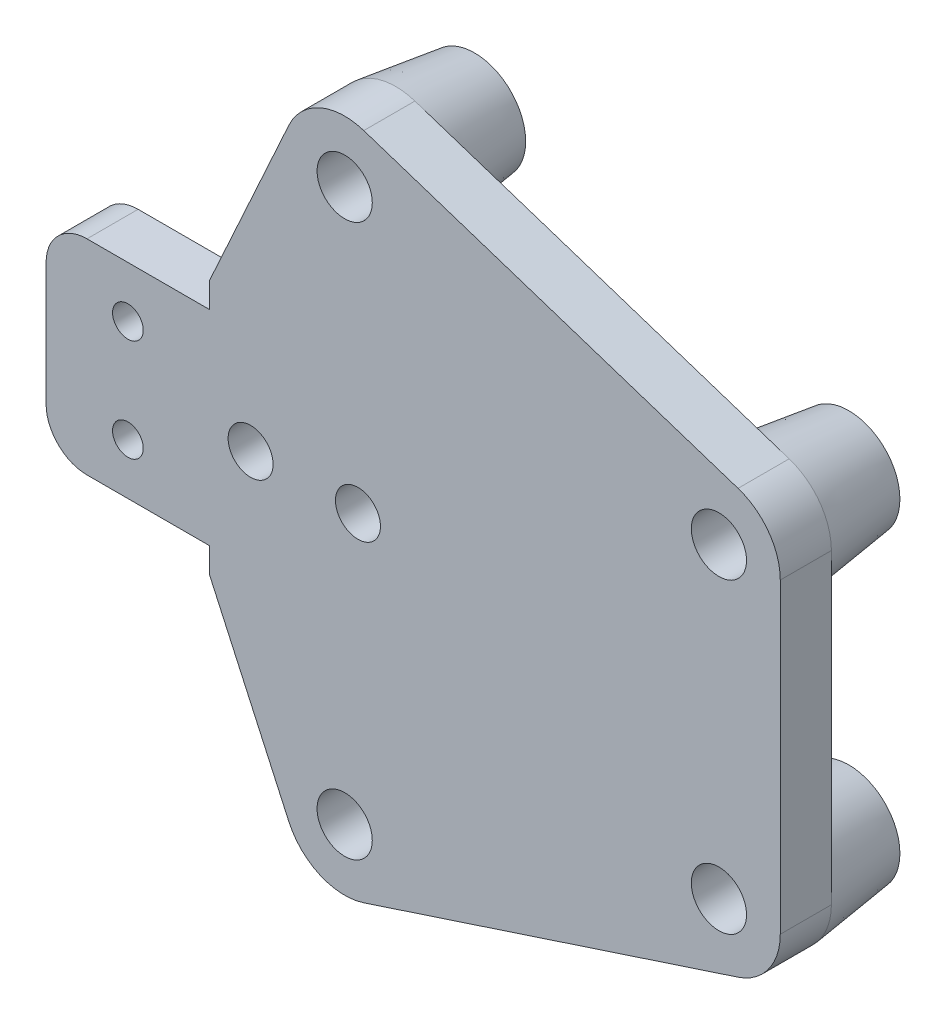
SolidWorks part; units mm, degrees
ref_plane "前视基准面" through (0, 0, 0) normal (0, 0, 1) x (1, 0, 0)
ref_plane "上视基准面" through (0, 0, 0) normal (0, 1, 0) x (1, 0, 0)
ref_plane "右视基准面" through (0, 0, 0) normal (1, 0, 0) x (0, 0, -1)
sketch "草图1" plane through (0, 0, 0) normal (0, 0, 1) x (1, 0, 0)
  line L0 (-612.4365, 0) -> (30009.3904, 0) construction
  line L1 (-611.4109, 10) -> (30010.416, 10) construction
  line L2 (-607.9921, -10) -> (30013.8348, -10) construction
  line L3 (0, -612.4365) -> (0, 30009.3904) construction
  line L4 (-10, -612.4365) -> (-10, 30009.3904) construction
  line L5 (10, -614.6741) -> (10, 30007.1528) construction
  line L6 (-24.3, 27) -> (-24.3, -27) construction
  line L7 (-16.4307, 32.7014) -> (20.1693, 20.7014)
  line L8 (24.3, 15) -> (24.3, -15)
  line L9 (-31.5, 12.5) -> (-31.5, -12.5)
  line L10 (-23.76, -29.4877) -> (-31.5, -12.5)
  line L11 (-31.5, 12.3) -> (-12, 12.3)
  line L12 (-31.5, 10.3) -> (-12, 10.3)
  line L13 (-12, 12.3) -> (-12, 10.3)
  line L14 (20.1693, -20.7014) -> (-16.4307, -32.7014)
  line L15 (-31.5, -10.3) -> (-12, -10.3)
  line L16 (-31.5, -12.3) -> (-12, -12.3)
  line L17 (-12, -12.3) -> (-12, -10.3)
  line L18 (-23.76, 29.4877) -> (-31.5, 12.5)
  line L19 (-33.5, 10) -> (-33.5, -10) construction
  line L20 (-47.5, 6) -> (-47.5, -6)
  line L21 (-43.5, 10) -> (-31.5, 10)
  line L22 (-43.5, -10) -> (-31.5, -10)
  circle A0 centre (18.3, 27) radius 11.5 construction
  circle A1 centre (-18.3, 27) radius 11.5 construction
  circle A2 centre (-18.3, -27) radius 11.5 construction
  circle A3 centre (18.3, 15) radius 11.5 construction
  circle A4 centre (18.3, 15) radius 2.7
  circle A5 centre (-18.3, 27) radius 6
  circle A6 centre (-16, 14) radius 1.7 construction
  circle A7 centre (18.3, 15) radius 5 construction
  circle A8 centre (-18.3, 27) radius 2.7
  circle A9 centre (-18.3, -27) radius 2.7
  circle A10 centre (-18.3, 27) radius 5 construction
  circle A11 centre (-18.3, -27) radius 5 construction
  circle A12 centre (18.3, 15) radius 6
  circle A13 centre (18.3, -15) radius 5 construction
  circle A14 centre (-16, -14) radius 1.7 construction
  circle A15 centre (-18.3, -27) radius 6
  circle A16 centre (-17, 0) radius 2.2
  circle A17 centre (-27.5, 0) radius 2.2
  circle A18 centre (-31, 18) radius 2.2 construction
  circle A19 centre (-31, -18) radius 2.2 construction
  circle A20 centre (18.3, -15) radius 11.5 construction
  circle A21 centre (18.3, -15) radius 6
  circle A22 centre (18.3, -15) radius 2.7
  circle A23 centre (-17, 0) radius 4 construction
  circle A24 centre (-39.5, 5) radius 1.5
  circle A25 centre (-39.5, -5) radius 1.5
  arc A26 (-47.5, -6) -> (-43.5, -10) centre (-43.5, -6) ccw
  arc A27 (-47.5, 6) -> (-43.5, 10) centre (-43.5, 6) cw
  point P48 (-31.5, 0)
  point P54 (-31.5, 0)
  point P82 (-47.5, -10)
  point P85 (-47.5, 10)
  dimension "D5" = 23
  dimension "D6" = 27
  dimension "D7" = 15
  dimension "D9" = 12
  dimension "D10" = 8
  dimension "D11" = 5.4
  dimension "D12" = 10
  dimension "D8" = 4.4
  dimension "D23" = 3.4
  dimension "D24" = 4.4
  dimension "D30" = 3
  dimension "D35" = 4
  dimension "D1" = 20
  dimension "D2" = 10
  dimension "D3" = 20
  dimension "D4" = 10
  dimension "D13" = 18.3
  dimension "D14" = 4
  dimension "D15" = 10.3
  dimension "D16" = 2
  dimension "D17" = 12.5
  dimension "D18" = 10.5
  dimension "D19" = 14.3
  dimension "D20" = 24.6
  dimension "D21" = 16
  dimension "D22" = 4
  dimension "D25" = 8
  dimension "D26" = 21
  dimension "D27" = 21.5
  dimension "D28" = 12
  dimension "D29" = 5
  dimension "D31" = 10
  dimension "D32" = 6
  dimension "D33" = 6
  dimension "D34" = 14
extrude "凸台-拉伸1" add sketch "草图1" along normal blind 5 contours L6 A11 A10 | A10 A8 | A4 | A11 A9 | L13 L11 L12 | L16 L17 L15 | L14 A21 L8 A12 L7 A5 L18 L11 L13 L12 L9 L15 L17 L16 L10 A15 A16 A17 | A21 A22 | A27 L20 A26 L22 L9 L21 A24 A25 region at (-4.862, 0, 0) region at (-13.5786, 30.4207, 0) region at (23.0214, 18.4207, 0) region at (23.0214, -18.4207, 0) region at (-21.75, 11.3, 0) region at (-20.6412, -32.3396, 0) region at (-39.3368, 0, 0) region at (-21.75, -11.3, 0)
ref_axis "基准轴1" through (-18.3, 27, 5) along (0, 0, -1)
ref_axis "基准轴2" through (18.3, 15, 5) along (0, 0, -1)
ref_plane "基准面2" through (6.2169, 18.9617, 0) normal (-0.3116, -0.9502, 0) x (-0.9502, 0.3116, 0)
sketch "草图4" plane through (6.2169, 18.9617, 0) normal (-0.3116, -0.9502, 0) x (-0.9502, 0.3116, 0)
  line L1 (-7.7159, 7.7) -> (-10.0159, 7.7)
  line L2 (25.8011, 0) -> (25.8011, 29798.822) construction
  line L3 (-6.7159, 0) -> (-7.7159, 7.7)
  line L4 (-10.0159, 0) -> (-6.7159, 0)
  line L5 (-10.0159, 7.7) -> (-10.0159, 0)
  line L10 (25.8011, -5) -> (25.8011, 0) construction
  line L11 (-12.7159, -4.4528) -> (-12.7159, 29794.3692) construction
  line L12 (-12.7159, -5) -> (-12.7159, 0) construction
  line L13 (25.8011, 0) -> (28.5011, 0) construction
  line L14 (31.7643, 0) -> (25.8011, 0) construction
  line L16 (28.5011, 0) -> (31.8011, 0)
  line L17 (31.8011, 0) -> (30.8011, 7.7)
  line L18 (30.8011, 7.7) -> (28.5011, 7.7)
  line L19 (28.5011, 7.7) -> (25.8011, 7.7) construction
  line L20 (28.5011, 7.7) -> (28.5011, 0)
  line L21 (25.8011, 7.7) -> (25.8011, 0) construction
  point P7 (0, 0)
  dimension "D2" = 2
  dimension "D3" = 5
  dimension "D7" = 2.7
  dimension "D8" = 6
  dimension "D9" = 7.7
  dimension "D10" = 5
revolve "旋转1" add sketch "草图4" angle 360 about L11 region at (14.3899, 16.282, -3.6208)
revolve "旋转2" add sketch "草图4<3>" angle 360 about L2 region at (-22.2101, 28.282, -3.6208)
sketch "草图4<3>" plane through (6.2169, 18.9617, 0) normal (-0.3116, -0.9502, 0) x (-0.9502, 0.3116, 0) same geometry as "草图4"
mirror "镜向1" about plane through (0, 0, 0) normal (0, 1, 0) of "旋转2", "旋转1"
extrude "凸台-拉伸2" add sketch "草图1<4>" against normal blind 6.8 contours L13 L11 L12 | L16 L17 L15 region at (-21.75, 11.3, 0) region at (-21.75, -11.3, 0)
sketch "草图1<4>" plane through (0, 0, 0) normal (0, 0, 1) x (1, 0, 0) same geometry as "草图1"
chamfer "倒角1" distance 3 distance2 6.8 1 edges at (-21.75, 12.3, 0) first distance on face at (-20.6604, 1.2592, 0)
chamfer "倒角2" distance 6.8 distance2 3 1 edges at (-21.75, -12.3, 0) first distance on face at (-21.75, -12.3, -3.4)
sketch "草图5" plane through (0, 0, 0) normal (0, 0, -1) x (-1, 0, 0)
  line L0 (39.5, 5) -> (39.5, -5) construction
  line L1 (41, 5) -> (41, -5)
  line L2 (38, 5) -> (38, -5)
  arc A0 (41, 5) -> (38, 5) centre (39.5, 5) ccw
  arc A1 (38, -5) -> (41, -5) centre (39.5, -5) ccw
  circle A2 centre (39.5, -5) radius 1.5 construction
  point P4 (39.5, 0)
extrude "切除-拉伸1" cut sketch "草图5" against normal blind 2.5
